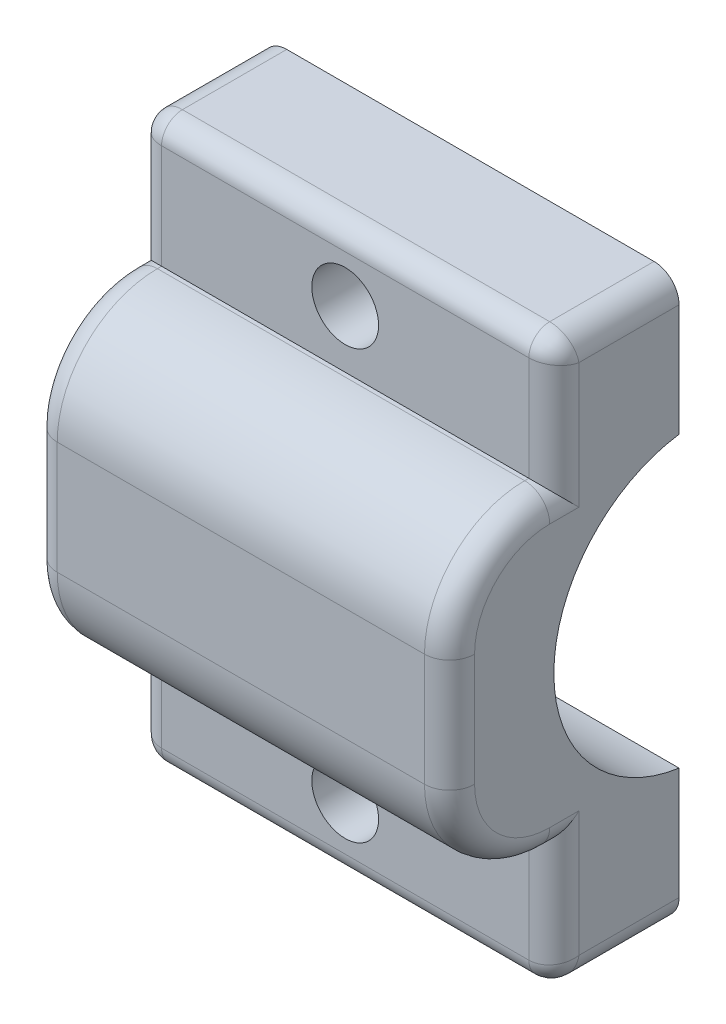
SolidWorks part; units mm, degrees
ref_plane "Plan de face" through (0, 0, 0) normal (0, 0, 1) x (1, 0, 0)
ref_plane "Plan de dessus" through (0, 0, 0) normal (0, 1, 0) x (1, 0, 0)
ref_plane "Plan de droite" through (0, 0, 0) normal (1, 0, 0) x (0, 0, -1)
sketch "Esquisse1" plane through (0, 0, 0) normal (0, 0, 1) x (1, 0, 0)
  line L1 (10, 13.5) -> (-10, 13.5)
  line L2 (10, 13.5) -> (10, -13.5)
  line L3 (10, -13.5) -> (-10, -13.5)
  line L4 (-10, 13.5) -> (-10, -13.5)
  line L5 (10, 13.5) -> (-10, -13.5) construction
  line L6 (10, -13.5) -> (-10, 13.5) construction
  point P0 (0, 0)
  dimension "D1" = 20
  dimension "D2" = 27
extrude "BASE" add sketch "Esquisse1" along normal blind 12
sketch "Esquisse2" plane through (-10, 0, 0) normal (-1, 0, 0) x (0, 0, 1)
  line L0 (0, 13.5) -> (0, -13.5) construction
  arc A0 (0, 7) -> (0, -7) centre (0, 0) cw
  dimension "D1" = 7
extrude "Passage_Guidon" cut sketch "Esquisse2" against normal through all and the other way through all flip side to cut
sketch "Esquisse5" plane through (0, 0, 12) normal (0, 0, 1) x (1, 0, 0)
  line L0 (10, 13.5) -> (-10, 13.5) construction
  line L1 (6.6, 0) -> (-6.6, 0) construction
  circle A0 centre (0, 10.25) radius 1.6
  circle A1 centre (0, -10.25) radius 1.6
  dimension "D1" = 3.2
  dimension "D2" = 3.25
extrude "Passage_Vis" cut sketch "Esquisse5" against normal up to next
sketch "Esquisse7" plane through (-10, 0, 0) normal (-1, 0, 0) x (0, 0, 1)
  line L0 (0, 13.5) -> (0, 7) construction
  line L1 (12, 13.5) -> (7, 13.5)
  line L2 (12, 13.5) -> (12, 7.5)
  line L3 (12, 7.5) -> (7, 7.5)
  line L4 (7, 13.5) -> (7, 7.5)
  line L5 (6.6, 0) -> (-6.6, 0) construction
  line L6 (12, -7.5) -> (7, -7.5)
  line L7 (7, -13.5) -> (7, -7.5)
  line L8 (12, -13.5) -> (7, -13.5)
  line L9 (12, -13.5) -> (12, -7.5)
  dimension "D1" = 6
  dimension "D2" = 7
extrude "Reduction" cut sketch "Esquisse7" against normal up to next
fillet "Congé1" radius 1 2 edges at (0, 13.5, 7) (0, -13.5, 7)
fillet "Congé2" radius 4.8 2 edges at (0, 7.5, 12) (0, -7.5, 12)
fillet "Congé3" radius 1.2 22 edges at (-10, 13.5, 3) (-10, 13.2071, 6.7071) (-10, 10, 7) (-10, 6.0941, 10.5941) (-10, 0, 12) (-10, -6.0941, 10.5941) (-10, -10, 7) (-10, -13.2071, 6.7071) (10, 13.5, 3) (10, 13.2071, 6.7071) (10, 10, 7) (10, 6.0941, 10.5941) (10, 0, 12) (10, -6.0941, 10.5941) (10, -10, 7) (10, -13.2071, 6.7071) (-10, -13.5, 3) (10, -13.5, 3) (-10, -7.5, 7.1) (10, -7.5, 7.1) (10, 7.5, 7.1) (-10, 7.5, 7.1)
sketch "Esquisse8" plane through (0, 0, 0) normal (1, 0, 0) x (0, 0, -1)
  line L0 (0, -13.5) -> (-6, -13.5) construction
  line L1 (0, 13.5) -> (-1, 13.5)
  line L2 (0, 13.5) -> (0, -13.5)
  line L3 (0, -13.5) -> (-1, -13.5)
  line L4 (-1, 13.5) -> (-1, -13.5)
  point P18 (0, 0)
  dimension "D1" = 1
extrude "Raccourcis_Serrage" cut sketch "Esquisse8" against normal through all both and the other way through all
